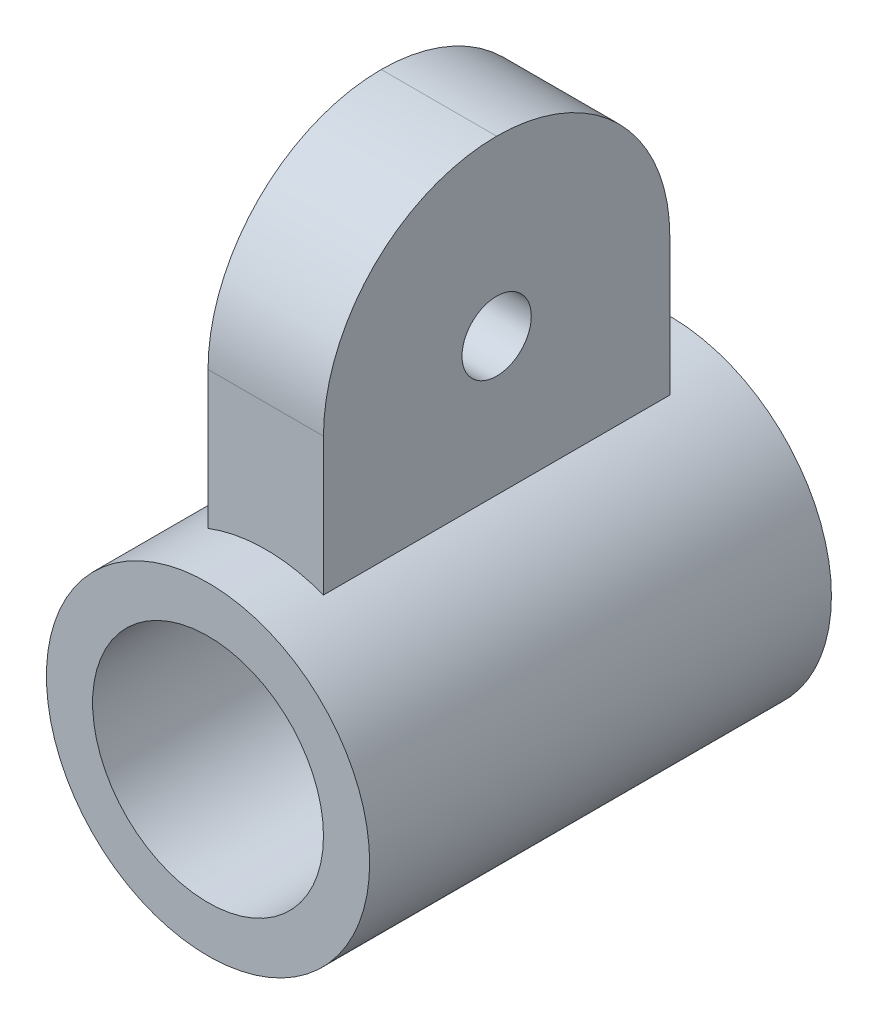
SolidWorks part; units mm, degrees
ref_plane "Front Plane" through (0, 0, 0) normal (0, 0, 1) x (1, 0, 0)
ref_plane "Top Plane" through (0, 0, 0) normal (0, 1, 0) x (1, 0, 0)
ref_plane "Right Plane" through (0, 0, 0) normal (1, 0, 0) x (0, 0, -1)
sketch "Sketch1" plane through (0, 0, 0) normal (0, 0, 1) x (1, 0, 0)
  circle A0 centre (0, 0) radius 10
  circle A1 centre (0, 0) radius 14
  dimension "D1" = 20
  dimension "D2" = 28
extrude "Boss-Extrude1" add sketch "Sketch1" along normal mid plane 40
sketch "Sketch3" plane through (0, 0, 0) normal (0, 1, 0) x (1, 0, 0)
  line L0 (-6, 0) -> (14, 0) construction
  line L1 (14, -20) -> (14, 20) construction
  dimension "D1" = 20
ref_plane "Plane1" through (0, 40, 0) normal (0, 1, 0) x (1, 0, 0)
sketch "Sketch4" plane through (0, 40, 0) normal (0, 1, 0) x (1, 0, 0)
  line L1 (-5, 15) -> (5, 15)
  line L2 (-5, 15) -> (-5, -15)
  line L3 (-5, -15) -> (5, -15)
  line L4 (5, 15) -> (5, -15)
  line L5 (-5, 15) -> (5, -15) construction
  line L6 (-5, -15) -> (5, 15) construction
  point P0 (0, 0)
  dimension "D1" = 10
  dimension "D2" = 30
extrude "Boss-Extrude2" add sketch "Sketch4" against normal up to surface (26.9233 mm away) up to face at (14, 0, 20)
fillet "Fillet1" radius 15 2 edges at (0, 40, 15) (0, 40, -15)
sketch "Sketch5" plane through (-5, 0, 0) normal (-1, 0, 0) x (0, 0, 1)
  circle A0 centre (0, 25) radius 3
  arc A1 (0, 40) -> (-15, 25) centre (0, 25) ccw construction
  dimension "D1" = 6
extrude "Cut-Extrude1" cut sketch "Sketch5" against normal up to next
equation "\"shaft inner diameter\"= 15mm "
equation "\"shaft outer diameter\"= 20mm "
equation "\"keyway_height\" = 1.39mm "
equation "\"keyway_width\" = 2.78mm "
equation "\"keyway_length\" = 30mm "
equation "\"steering column length\" = 555mm "
equation "\"steering wheel bolt width\" = 6mm "
equation "\"steering wheel bolt length\" = 40mm "
equation "\"bushing length\" = 40mm "
equation "\"bushing thickness\" = 3mm "
equation "\"u_joint clearance\" = 30mm "
equation "\"u_joint thickness\" = 7.5mm "
equation "\"horizontal shaft length\" = 90mm "
equation "\"short_bearing_outer_width\" = 10mm "
equation "\"column bushing diameter\" = \"primary shaft small diameter\" + 4 "
equation "\"column bushing distance\" = \"steering column length\"/4 "
equation "\"pinion width\" = 26.5mm "
equation "\"number of teeth\" = 18mm "
equation "\"D1@Sketch1\"=(\"primary shaft large diameter\"+\"primary shaft small diameter\")/2"
equation "\"D1@Boss-Extrude1\"=\"bushing length\""
equation "\"D1@Sketch3\"=\"shaft outer diameter\""
equation "\"column angle\" = 45deg "
equation "\"D2@Sketch1\"=(\"primary shaft large diameter\" + \"primary shaft small diameter\")/2+(\"primary shaft large diameter\"-\"secondary shaft small diameter\")"
equation "\"wheel base\" = 1561mm "
equation "\"track\" = 1354mm "
equation "\"turning radius\" = 2000mm "
equation "\"turn to lock\" = 0.75mm "
equation "\"steering arm length\" = 100mm "
equation "\"primary shaft small diameter\" = 16mm "
equation "\"primary shaft large diameter\" = 24mm "
equation "\"secondary shaft small diameter\" = 16mm "
equation "\"secondary shaft large diameter\" = 25mm "
equation "\"pin hole diameter\" = 10mm "
equation "\"rack hole to hole\" = 500mm "
equation "\"rack length\" = \"rack hole to hole\" + \"pin hole diameter\"*2 "
equation "\"max turning angle\" = atn(\"wheel base\" / (\"turning radius\" - 0.5 * \"track\")) "
equation "\"max travel\" = 2 * \"steering arm length\" * sin(0.5 * \"max turning angle\") "
equation "\"pitch diameter\" = \"max travel\"/(pi * \"turn to lock\") "
equation "\"pressure angle\" = 20deg "
equation "\"module\" = \"pitch diameter\" / \"number of teeth\" "
equation "\"tie rod length\" = 305mm "
equation "\"tie rod inner diameter\" = 6.6mm "
equation "\"tie rod outer diameter\" = 8.1mm "
